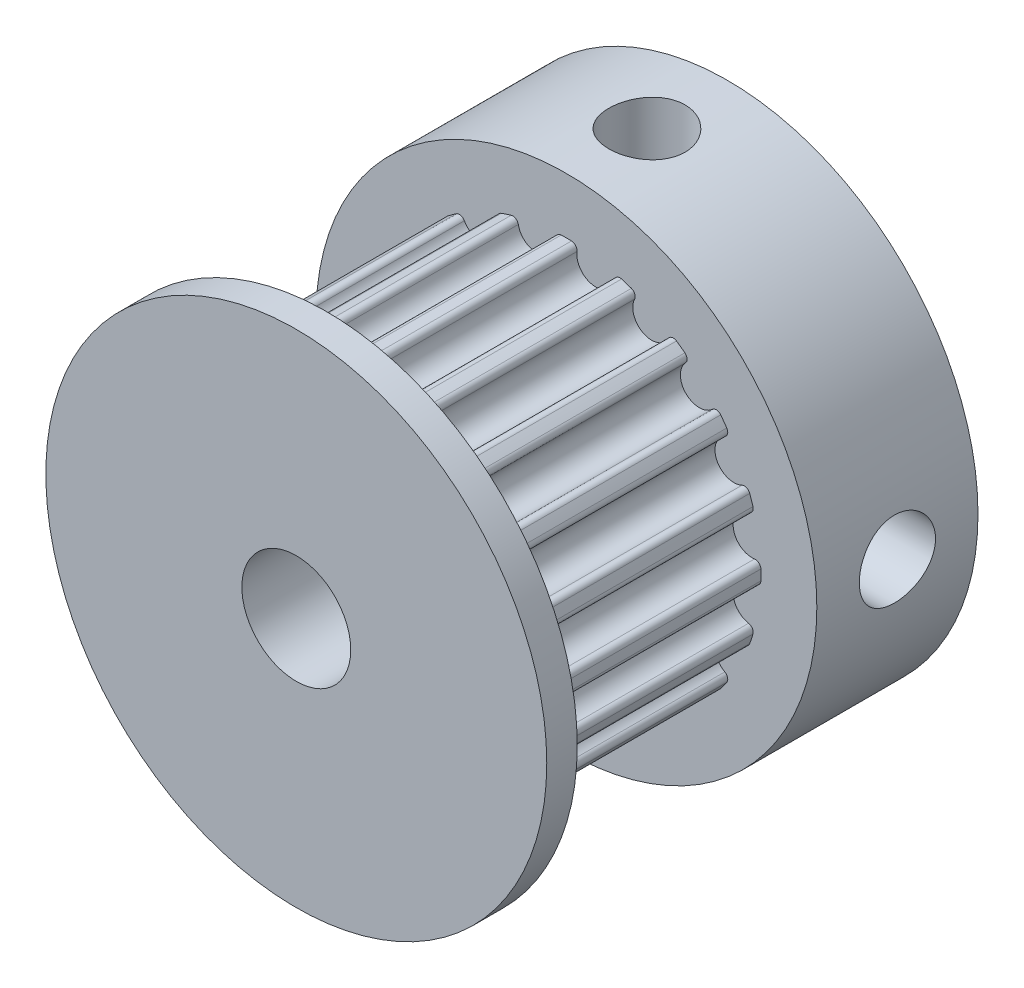
SolidWorks part; units mm, degrees
ref_plane "Front Plane" through (0, 0, 0) normal (1, 0, 0) x (0, 1, 0)
ref_plane "Top Plane" through (0, 0, 0) normal (0, 0, 1) x (0, 1, 0)
ref_plane "Right Plane" through (0, 0, 0) normal (0, 1, 0) x (-1, 0, 0)
other "Configuration Table"
sketch "Sketch2" plane through (0, 0, 0) normal (0, 0, 1) x (0, 1, 0)
  line L0 (0, 0) -> (0, 8.9343)
  line L1 (0, 0) -> (1.2146, 7.6687) construction
  line L2 (1.2146, 7.6687) -> (1.3507, 8.528) construction
  line L3 (0, 0) -> (2.7608, 8.497)
  arc A3 (0.572, 8.916) -> (2.2112, 8.6563) centre (1.3507, 8.528) ccw
  arc A4 (0, 8.9343) -> (0.572, 8.916) centre (0, 0) cw
  arc A5 (2.2112, 8.6563) -> (2.7608, 8.497) centre (0, 0) cw
  dimension "D1" = 8.9343
  dimension "D2" = 7.7643
  dimension "D3" = 9
  dimension "D4" = 0.87
  dimension "D5" = 8.9343
  dimension "D6" = 9
extrude "Boss-Extrude1" add sketch "Sketch2" along normal blind 11 contours A5 A3 A4 L0 L3 region at (-5.4794, 0.8679, 0)
fillet "Fillet2" radius 0.26 2 edges at (-8.6563, 2.2112, 5.5) (-8.916, 0.572, 5.5)
pattern_circular "CirPattern12" count 20 over 360 about axis through (0, 0, 11) along (0, 0, -1) of "Fillet2", "Boss-Extrude1"
sketch "Sketch3" plane through (0, 0, 0) normal (0, 0, 1) x (0, 1, 0)
  circle A0 centre (0, 0) radius 11.5
  circle A1 centre (0, 0) radius 2.5
  dimension "D1" = 23
  dimension "D2" = 5
extrude "Boss-Extrude2" add sketch "Sketch3" against normal blind 7.4 contours A1 | A0 A1 region at (0, -11.1747, 0) region at (0, 0, 0)
extrude "Boss-Extrude3" add sketch "Sketch3<3>" along normal blind 1.4 from surface contours A1 | A0 A1 region at (0, -11.1747, 0) region at (0, 0, 0) starting at face at (0, 0, 11)
sketch "Sketch3<3>" plane through (0, 0, 0) normal (0, 0, 1) x (0, 1, 0) same geometry as "Sketch3"
extrude "Cut-Extrude1" cut sketch "Sketch3<4>" against normal through all both and the other way through all contours A1 region at (0, 0, 0)
sketch "Sketch3<4>" plane through (0, 0, 0) normal (0, 0, 1) x (0, 1, 0) same geometry as "Sketch3"
ref_plane "Plane1" through (11.5, 0, 0) normal (1, 0, 0) x (0, 0, -1)
ref_plane "Plane2" through (0, 11.5, 0) normal (0, 1, 0) x (0, 0, 1)
sketch "Sketch4" plane through (11.5, 0, 0) normal (1, 0, 0) x (0, 0, -1)
  line L0 (0, 11.5) -> (0, -11.5) construction
  line L1 (0, 11.5) -> (0, -11.5)
  line L2 (7.4, -11.5) -> (7.4, 11.5) construction
  line L3 (7.4, -11.5) -> (7.4, 11.5)
  line L4 (7.4, 0) -> (0, 0) construction
  circle A0 centre (3.7, 0) radius 1.75
  dimension "D1" = 3.5
sketch "Sketch5" plane through (0, 11.5, 0) normal (0, 1, 0) x (0, 0, 1)
  line L0 (0, -11.5) -> (0, 11.5) construction
  line L1 (-7.4, 11.5) -> (-7.4, -11.5) construction
  line L2 (0, -11.5) -> (0, 11.5)
  line L3 (-7.4, 11.5) -> (-7.4, -11.5)
  line L4 (-7.4, 0) -> (0, 0) construction
  circle A0 centre (-3.7, 0) radius 1.75
  dimension "D1" = 3.5
extrude "Cut-Extrude2" cut sketch "Sketch4" against normal up to vertex (11.5 mm away) and the other way through all contours A0 up to point (0, 0, 0)
extrude "Cut-Extrude3" cut sketch "Sketch5" against normal up to vertex (11.5 mm away) contours A0 up to point (0, 0, 0)
equation "\"Pitch\"= 3mm"
equation "\"Teeth\" = 20"
equation "\"Shaft\" = 5mm"
equation "\"BeltHeight\"= 10 + 1"
equation "\"PitchDiameter\"= \"Pitch\" * \"Teeth\" / PI * 1mm"
equation "\"D1@Sketch2\"=\"PitchDiameter\"/2 - 0.615"
equation "\"D2@Sketch2\"=\"D1@Sketch2\"-1.17"
equation "\"D3@Sketch2\"= 180 / \"Teeth\""
equation "\"D1@Boss-Extrude1\"=\"BeltHeight\""
equation "\"D5@Sketch2\"=\"D1@Sketch2\""
equation "\"D6@Sketch2\"=\"D3@Sketch2\""
equation "\"D1@CirPattern12\"=\"Teeth\""
equation "\"Diameter\" = 23"
equation "\"D1@Sketch3\"=\"Diameter\""
equation "\"D2@Sketch3\"=\"Shaft\""
